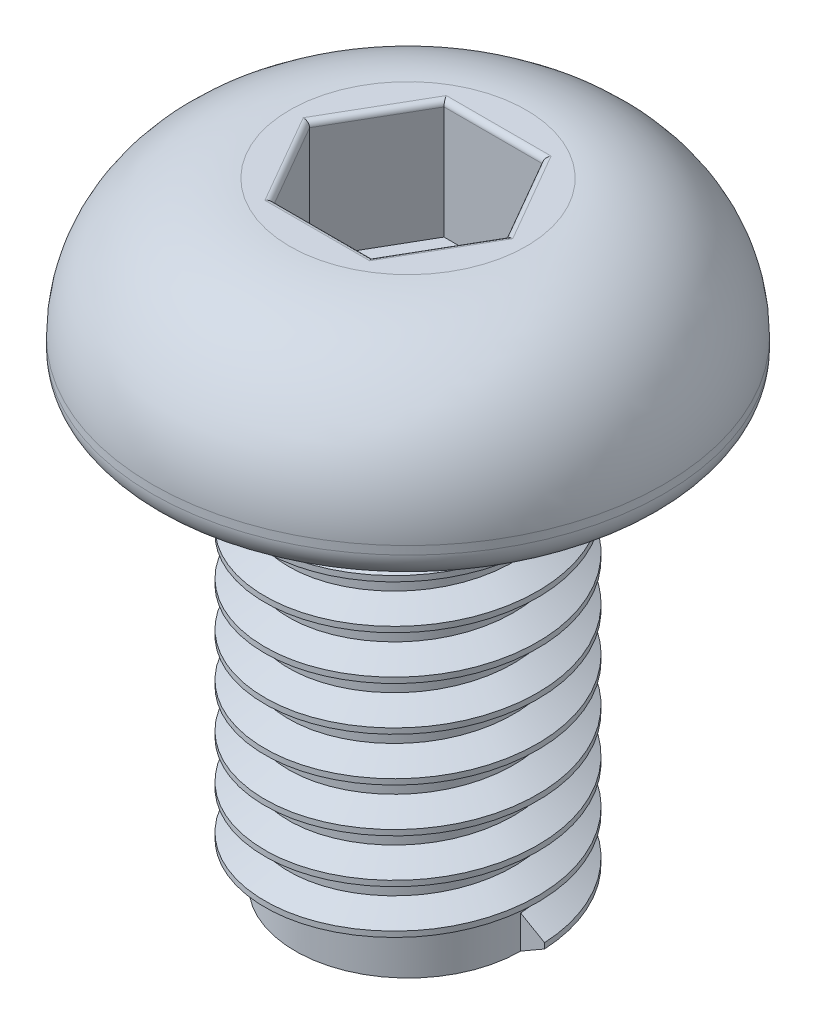
SolidWorks part; units mm, degrees
ref_plane "Front Plane" through (0, 0, 0) normal (0, 0, 1) x (1, 0, 0)
ref_plane "Top Plane" through (0, 0, 0) normal (0, 1, 0) x (1, 0, 0)
ref_plane "Right Plane" through (0, 0, 0) normal (1, 0, 0) x (0, 0, -1)
sketch "Sketch1" plane through (0, 0, 0) normal (0, 1, 0) x (1, 0, 0)
  circle A0 centre (0, 0) radius 2.05
  dimension "D1" = 4.1
extrude "Boss-Extrude1" add sketch "Sketch1" against normal blind 8
sketch "Sketch2" plane through (0, 0, 0) normal (0, 1, 0) x (1, 0, 0)
  circle A0 centre (0, 0) radius 4.65
  dimension "D1" = 9.3
extrude "Boss-Extrude2" add sketch "Sketch2" along normal blind 3.15
sketch "Sketch3" plane through (0, 3.15, 0) normal (0, 1, 0) x (1, 0, 0)
  line L1 (1.7898, 0) -> (0.8949, 1.55)
  line L2 (0.8949, 1.55) -> (-0.8949, 1.55)
  line L3 (-0.8949, 1.55) -> (-1.7898, 0)
  line L4 (-1.7898, 0) -> (-0.8949, -1.55)
  line L5 (-0.8949, -1.55) -> (0.8949, -1.55)
  line L6 (0.8949, -1.55) -> (1.7898, 0)
  circle A0 centre (0, 0) radius 1.55 construction
  dimension "D1" = 3.1
  dimension "D2" = 1.55
extrude "Cut-Extrude1" cut sketch "Sketch3" against normal blind 2.15
fillet "Fillet1" radius 2.5 1 edges at (0, 3.15, 4.65)
fillet "Fillet2" radius 0.5 1 edges at (0, 0, 4.65)
fillet "Fillet3" radius 0.1 6 edges at (0, 3.15, 1.55) (-1.3423, 3.15, 0.775) (1.3423, 3.15, 0.775) (1.3423, 3.15, -0.775) (-1.3423, 3.15, -0.775) (0, 3.15, -1.55)
thread "Thread1" pitch 0.8 method extrude profile "Thread Profile1" start angle 0, offset 0, length 0, pitch 0.8, diameter 4.1
ref_plane "Plane1" through (2.05, -8, 0) normal (0, 0, 1) x (1, 0, 0)
sketch "Thread Profile1" plane through (2.05, -8, 0) normal (0, 0, 1) x (1, 0, 0)
  line L0 (0, 0) -> (0, 0.8) construction
  line L1 (0, 0) -> (0.433, 0.25)
  line L2 (0.433, 0.25) -> (0.433, 0.35)
  line L3 (0.433, 0.35) -> (0, 0.6)
  line L4 (0.433, 0.3) -> (0, 0.3) construction
  line L11 (0, 0) -> (0, 0.6)
  point P2 (0, 0)
  dimension "Pitch" = 0.8
  dimension "Profile_Angle" = 60
  dimension "Profile_Land" = 0.1
  dimension "Profile_Height" = 0.433
